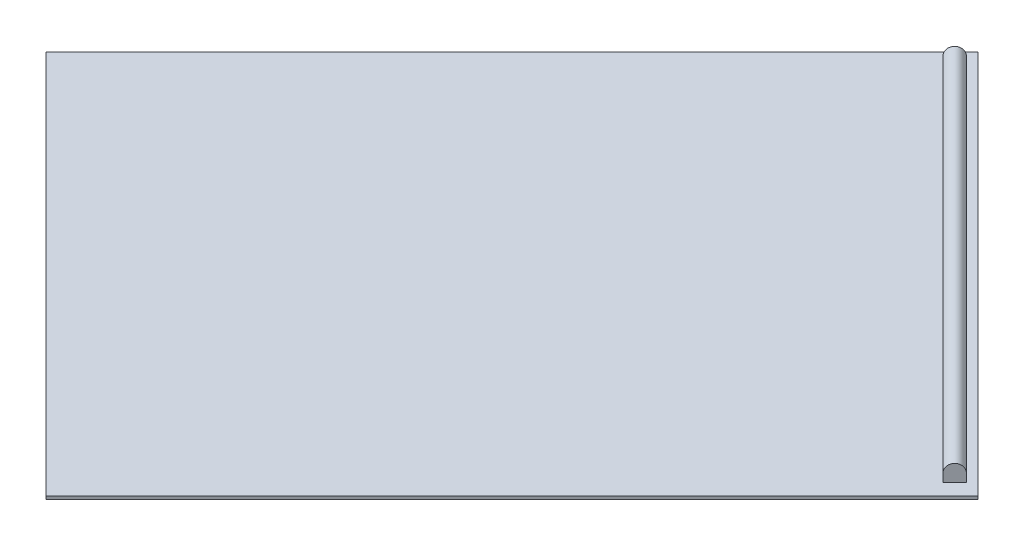
SolidWorks part; units mm, degrees
ref_plane "Front Plane" through (0, 0, 0) normal (0, 0, 1) x (1, 0, 0)
ref_plane "Top Plane" through (0, 0, 0) normal (0, 1, 0) x (1, 0, 0)
ref_plane "Right Plane" through (0, 0, 0) normal (1, 0, 0) x (0, 0, -1)
sketch "Sketch1" plane through (0, 0, 0) normal (0, 1, 0) x (1, 0, 0)
  line L0 (0, -0.4396) -> (0, 0.4515) construction
  line L1 (-0.4325, 0) -> (0.4116, 0) construction
  line L2 (-0.395, 0.395) -> (0.395, -0.395) construction
  line L4 (-49.4975, -516.188) -> (233.3452, -233.3452)
  line L5 (0, 0) -> (233.3452, -233.3452)
  line L6 (-49.4975, -516.188) -> (-282.8427, -282.8427)
  line L7 (0, 0) -> (-282.8427, -282.8427)
  dimension "D1" = 45
  dimension "D2" = 330
  dimension "D3" = 400
extrude "Boss-Extrude1" add sketch "Sketch1" along normal blind 2
sketch "Sketch4" plane through (0, 2, 0) normal (0, 1, 0) x (1, 0, 0)
  line L17 (3.5355, -10.6066) -> (-3.5355, -17.6777)
  line L18 (-3.5355, -17.6777) -> (215.6676, -236.8808)
  line L19 (215.6676, -236.8808) -> (222.7386, -229.8097)
  line L20 (222.7386, -229.8097) -> (3.5355, -10.6066)
  line L21 (0, 0) -> (-282.8427, -282.8427) construction
  line L22 (233.3452, -233.3452) -> (0, 0) construction
  dimension "D1" = 310
  dimension "D2" = 10
  dimension "D3" = 5
  dimension "D4" = 10
extrude "Boss-Extrude2" add sketch "Sketch4" along normal blind 10
sketch "Sketch6" plane through (7.0711, 0, 7.0711) normal (-0.7071, 0, -0.7071) x (-0.7071, 0, 0.7071)
  line L4 (15, 12) -> (15, 2) construction
  line L8 (5, 7) -> (5, 12)
  line L9 (5, 12) -> (15, 12)
  line L10 (5, 12) -> (15, 12) construction
  line L11 (15, 12) -> (15, 7)
  arc A0 (15, 7) -> (5, 7) centre (10, 7) ccw
  line M7 (15, 2) -> (15, 12)
  line M8 (15, 12) -> (5, 12)
  line M9 (5, 12) -> (5, 2)
extrude "Cut-Extrude1" cut sketch "Sketch6" against normal up to next contours A0 L9 M9 | A0 M7 M8 region at (-2.7458, 10.8832, 16.8879) region at (2.7458, 10.8832, 11.3963)
sketch "Sketch8" plane through (0, 2, 0) normal (0, 1, 0) x (1, 0, 0)
  line L1 (0, -7.0711) -> (-279.3072, -286.3782)
  line L2 (-282.8427, -282.8427) -> (-49.4975, -516.188) construction
  line L5 (233.3452, -233.3452) -> (0, 0)
  line L8 (0, -7.0711) -> (226.2742, -233.3452)
  line L10 (-279.3072, -286.3782) -> (-282.8427, -282.8427)
  line L11 (226.2742, -233.3452) -> (-53.033, -512.6524)
  line L12 (-53.033, -512.6524) -> (-49.4975, -516.188)
  line L13 (-49.4975, -516.188) -> (233.3452, -233.3452) construction
  line L14 (0, 0) -> (-282.8427, -282.8427) construction
  line L15 (-49.4975, -516.188) -> (233.3452, -233.3452)
  line L16 (-282.8427, -282.8427) -> (0, 0)
  dimension "D1" = 5
  dimension "D2" = 5
  dimension "D4" = 5
